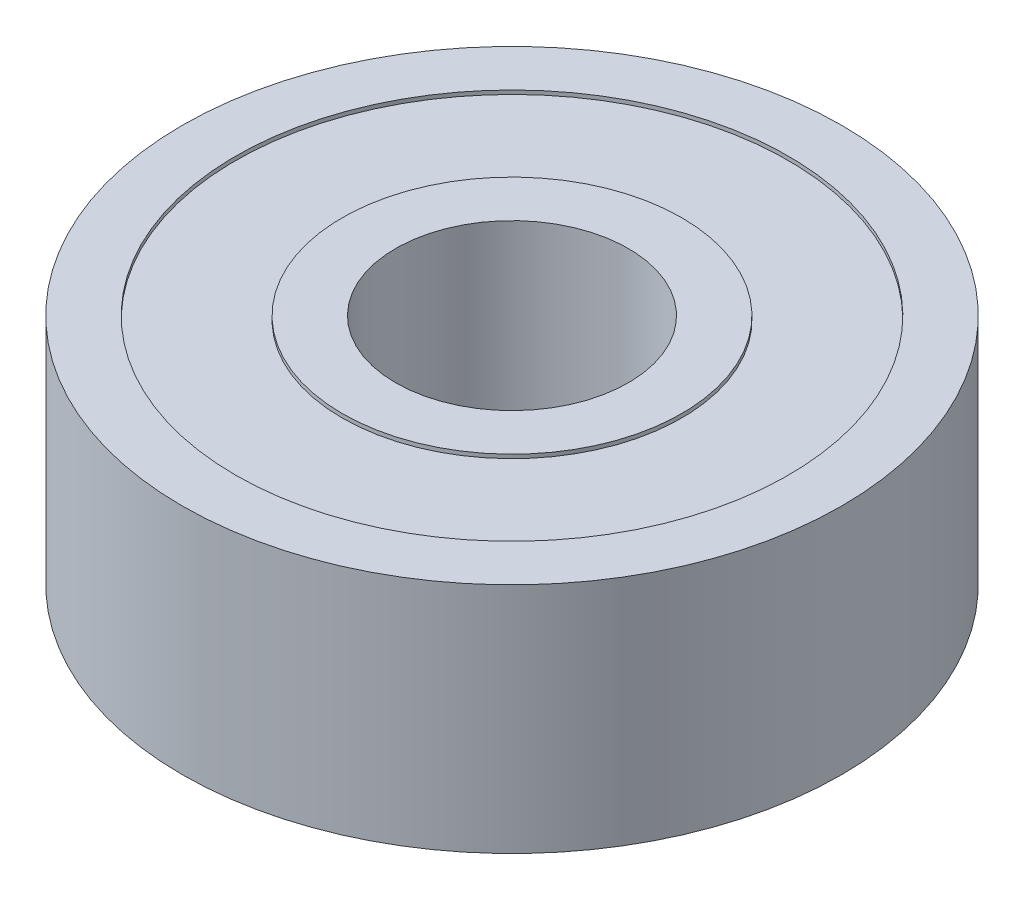
SolidWorks part; units mm, degrees
ref_plane "Front plane" through (0, 0, 0) normal (0, 0, 1) x (1, 0, 0)
ref_plane "Top plane" through (0, 0, 0) normal (0, 1, 0) x (1, 0, 0)
ref_plane "Right plane" through (0, 0, 0) normal (1, 0, 0) x (0, 0, -1)
ref_axis "Axis X" through (0, 0, 0) along (1, 0, 0)
ref_axis "Axis Y" through (0, 0, 0) along (0, 1, 0)
ref_axis "Axis Z" through (0, 0, 0) along (0, 0, 1)
sketch "Sketch1" plane through (0, 0, 0) normal (0, 1, 0) x (1, 0, 0)
  circle A0 centre (0, 0) radius 8.5
  circle A1 centre (0, 0) radius 3
  dimension "D1" = 17
  dimension "D2" = 6
extrude "Extrude1" add sketch "Sketch1" along normal blind 6
sketch "Sketch2" plane through (0, 6, 0) normal (0, 1, 0) x (1, 0, 0)
  circle A2 centre (0, 0) radius 7.125
  circle A3 centre (0, 0) radius 7.125
  circle A5 centre (0, 0) radius 4.375
  circle A6 centre (0, 0) radius 4.375
  dimension "D1" = 1.375
  dimension "D2" = 1.375
extrude "Extrude2" cut sketch "Sketch2" against normal blind 0.1
sketch "Sketch3" plane through (0, 0, 0) normal (0, -1, 0) x (1, 0, 0)
  circle A2 centre (0, 0) radius 7.125
  circle A3 centre (0, 0) radius 7.125
  circle A5 centre (0, 0) radius 4.375
  circle A6 centre (0, 0) radius 4.375
  dimension "D1" = 1.375
  dimension "D2" = 1.375
extrude "Extrude3" cut sketch "Sketch3" against normal blind 0.1
equation "\"motor_D\"= 30'Motor diameter"
equation "\"D1@Sketch1\"=\"bearing_d2\""
equation "\"D2@Sketch1\"=\"bearing_d1\""
equation "\"D1@Extrude1\"=\"bearing h\""
equation "\"D1@Sketch2\"=(\"bearing_d2\"-\"bearing_d1\")/2/4"
equation "\"D2@Sketch2\"=\"D1@Sketch2\""
equation "\"D1@Extrude2\"=0.1"
equation "\"D2@Sketch3\"=(\"bearing_d2\"-\"bearing_d1\")/2/4"
equation "\"D1@Sketch3\"=\"D2@Sketch3\""
equation "\"bearing_d1\"= 6'Bearing inner diameter"
equation "\"bearing_d2\"= 17'Bearing external diameter"
equation "\"bearing h\"= 6'Bearing heigh"
equation "\"pin_d\"= 2'Pin diameter"
equation "\"pin_h\"= 12'Pin heigh"
equation "\"print_offset\"= 0.2'Offset for printing holes"
equation "\"module_diameter\"= 41"
equation "\"motor_diameter\"= 32"
